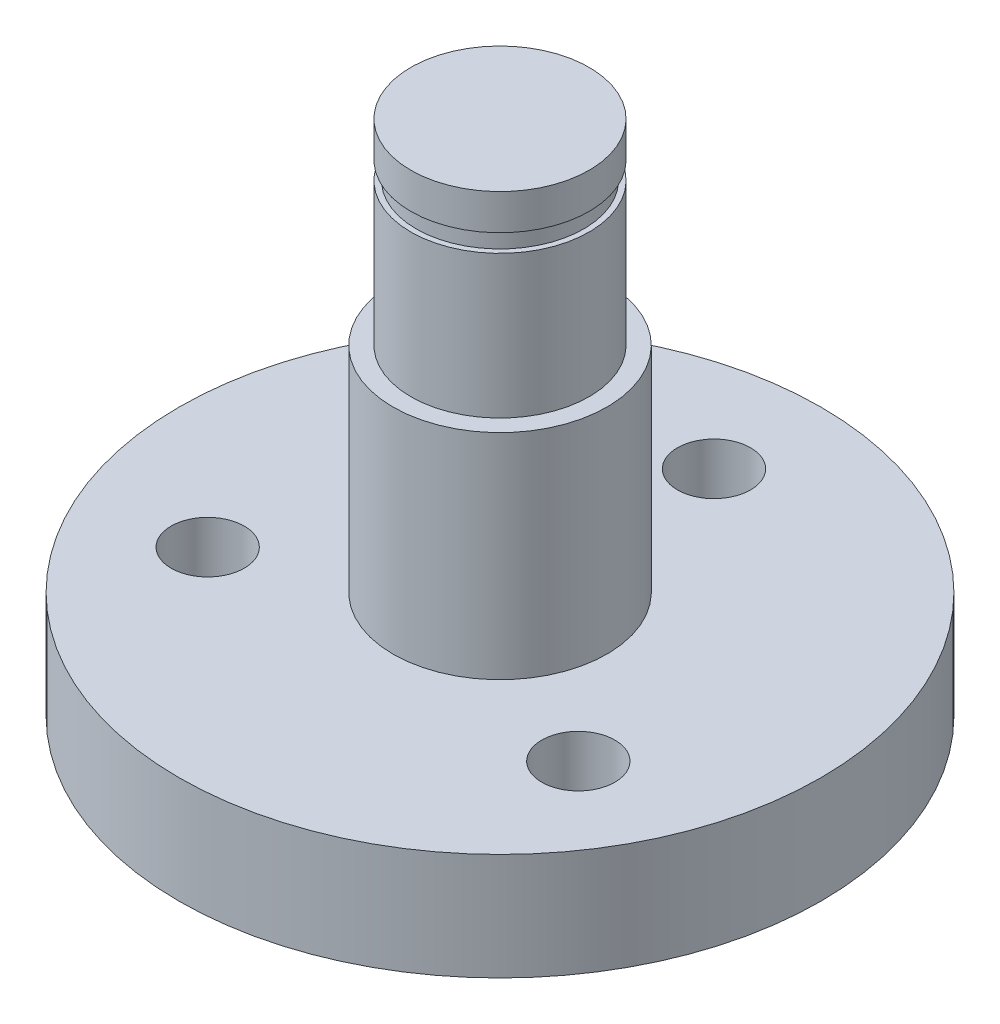
SolidWorks part; units mm, degrees
ref_plane "前视基准面" through (0, 0, 0) normal (0, 0, 1) x (1, 0, 0)
ref_plane "上视基准面" through (0, 0, 0) normal (0, 1, 0) x (1, 0, 0)
ref_plane "右视基准面" through (0, 0, 0) normal (1, 0, 0) x (0, 0, -1)
sketch "草图1" plane through (0, 0, 0) normal (0, 1, 0) x (1, 0, 0)
  circle A0 centre (0, 0) radius 3
  circle A1 centre (0, 0) radius 9
  circle A2 centre (5.1962, -3) radius 1.25
  circle A3 centre (-5.1962, -3) radius 1.25
  circle A4 centre (0, 6) radius 1.25
  circle A6 centre (0, 0) radius 2.5
  point P14 (0, 0)
  point P15 (0, 0)
  point P19 (0, 0)
  dimension "D1" = 3
sketch "草图6" plane through (0, 0, 0) normal (1, 0, 0) x (0, 0, -1)
  line L1 (-2.35, 10) -> (-2.35, 10.5)
  line L2 (-2.35, 10.5) -> (-2.5, 10.5)
  line L3 (-2.5, 10.5) -> (-2.5, 10)
  line L4 (0, 9) -> (0, 7.5) construction
  line L5 (-2.5, 10) -> (-2.35, 10)
extrude "凸台-拉伸1" add sketch "草图1" along normal blind 6 contours A0 A6 region at (-2.9151, 0, 0)
extrude "凸台-拉伸2" add sketch "草图1<8>" along normal blind 11.5 contours A6 region at (0, 0, 0)
sketch "草图1<8>" plane through (0, 0, 0) normal (0, 1, 0) x (1, 0, 0) same geometry as "草图1"
extrude "凸台-拉伸3" add sketch "草图1<9>" against normal blind 3 contours A1 A3 A4 A0 | A3 | A4 | A6 | A0 A6 | A2 region at (-2.9151, 0, 0) region at (-8.7454, 0, 0) region at (5.1962, 0, 3) region at (-5.1962, 0, 3) region at (0, 0, -6) region at (0, 0, 0)
sketch "草图1<9>" plane through (0, 0, 0) normal (0, 1, 0) x (1, 0, 0) same geometry as "草图1"
revolve "切除-旋转1" cut sketch "草图6" angle 360 about L4
hole_wizard "M2.5 螺纹孔1" positions "草图7" profile "草图8" tap size "M2.5" standard "GB" end condition through all
sketch "草图7" plane through (0, 0, 0) normal (0, 1, 0) x (1, 0, 0)
  point P0 (-5.1962, -3)
  point P3 (0, 6)
  point P6 (5.1962, -3)
sketch "草图8" plane through (-5.1962, 0, 3) normal (1, 0, 0) x (0, 0, 1)
  line L0 (0, 0) -> (0, 3)
  line L1 (0, 3) -> (1.025, 3)
  line L2 (1.025, 3) -> (1.025, 0)
  line L5 (1.025, 0) -> (0, 0)
  line L11 (0, -6.35) -> (0, 107.95) construction
  dimension "通孔螺纹孔钻头直径" = 2.05
  dimension "通孔螺纹孔钻头深度" = 3
cosmetic thread "孔螺蚊线1"
cosmetic thread "孔螺蚊线2"
cosmetic thread "孔螺蚊线3"
